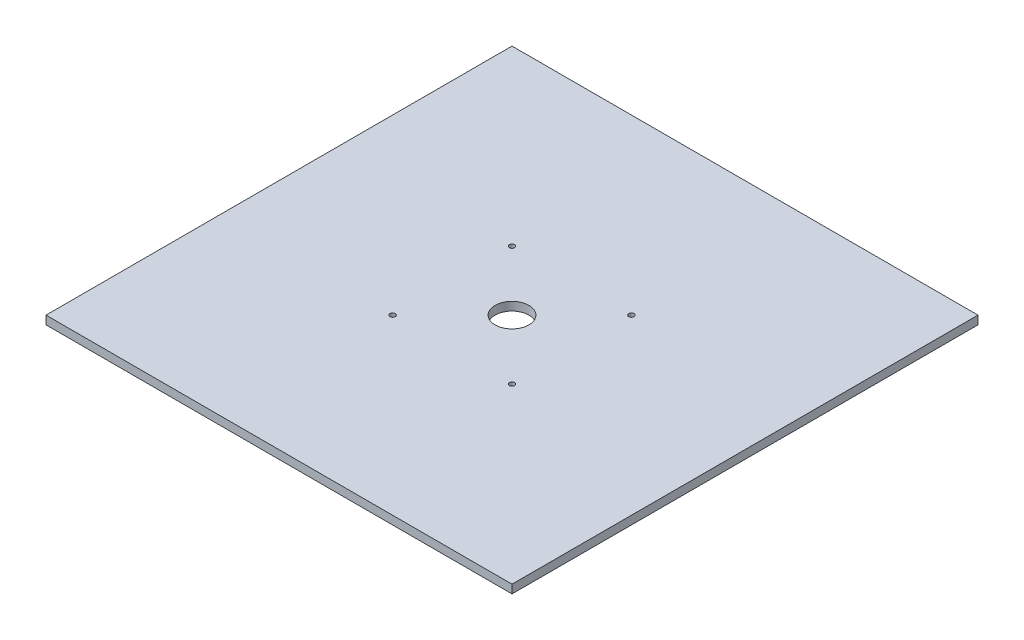
SolidWorks part; units mm, degrees
ref_plane "Front Plane" through (0, 0, 0) normal (0, 0, 1) x (1, 0, 0)
ref_plane "Top Plane" through (0, 0, 0) normal (0, 1, 0) x (1, 0, 0)
ref_plane "Right Plane" through (0, 0, 0) normal (1, 0, 0) x (0, 0, -1)
sketch "Sketch1" plane through (0, 0, 0) normal (0, 1, 0) x (1, 0, 0)
  line L1 (-175, -175) -> (175, -175)
  line L2 (-175, -175) -> (-175, 175)
  line L3 (-175, 175) -> (175, 175)
  line L4 (175, -175) -> (175, 175)
  line L5 (-175, -175) -> (175, 175) construction
  line L6 (-175, 175) -> (175, -175) construction
  point P0 (0, 0)
  dimension "D1" = 350
  dimension "D2" = 350
extrude "Boss-Extrude1" add sketch "Sketch1" along normal blind 6.35
sketch "Sketch2" plane through (0, 6.35, 0) normal (0, 1, 0) x (1, 0, 0)
  line L1 (-44.8437, -44.8437) -> (44.8437, -44.8437) construction
  line L2 (-44.8437, -44.8437) -> (-44.8437, 44.8437) construction
  line L3 (-44.8437, 44.8437) -> (44.8437, 44.8437) construction
  line L4 (44.8437, -44.8437) -> (44.8437, 44.8437) construction
  line L5 (-44.8437, -44.8437) -> (44.8437, 44.8437) construction
  line L6 (-44.8437, 44.8437) -> (44.8437, -44.8437) construction
  circle A0 centre (-44.8437, 44.8437) radius 1.9844
  circle A1 centre (44.8437, 44.8437) radius 1.9844
  circle A2 centre (-44.8437, -44.8437) radius 1.9844
  circle A3 centre (44.8437, -44.8437) radius 1.9844
  circle A4 centre (0, 0) radius 12.7
  point P0 (0, 0)
  dimension "D3" = 3.9688
  dimension "D4" = 25.4
  dimension "D1" = 89.6874
  dimension "D2" = 89.6874
extrude "Cut-Extrude1" cut sketch "Sketch2" against normal through all and the other way through all
